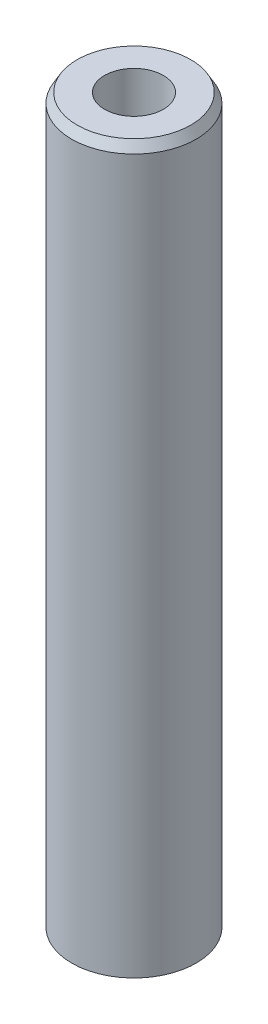
SolidWorks part; units mm, degrees
ref_plane "Front Plane" through (0, 0, 0) normal (0, 0, 1) x (1, 0, 0)
ref_plane "Top Plane" through (0, 0, 0) normal (0, 1, 0) x (1, 0, 0)
ref_plane "Right Plane" through (0, 0, 0) normal (1, 0, 0) x (0, 0, -1)
sketch "Sketch1" plane through (0, 0, 0) normal (0, 1, 0) x (1, 0, 0)
  circle A0 centre (0, 0) radius 25
  dimension "SHAFT_OD" = 50
extrude "Boss-Extrude1" add sketch "Sketch1" along normal blind 292.5597
sketch "Sketch2" plane through (0, 0, 0) normal (0, 1, 0) x (1, 0, 0)
  circle A0 centre (0, 0) radius 11.8044
  dimension "BORE_D" = 23.6088
extrude "Cut-Extrude1" cut sketch "Sketch2" along normal through all
chamfer "Chamfer1" distance 3.8009 angle 30 2 edges at (0, 292.5597, 25) (0, 0, 25) first distance on face at (0, 292.5597, 25) first distance on face at (0, 0, 11.8044)
